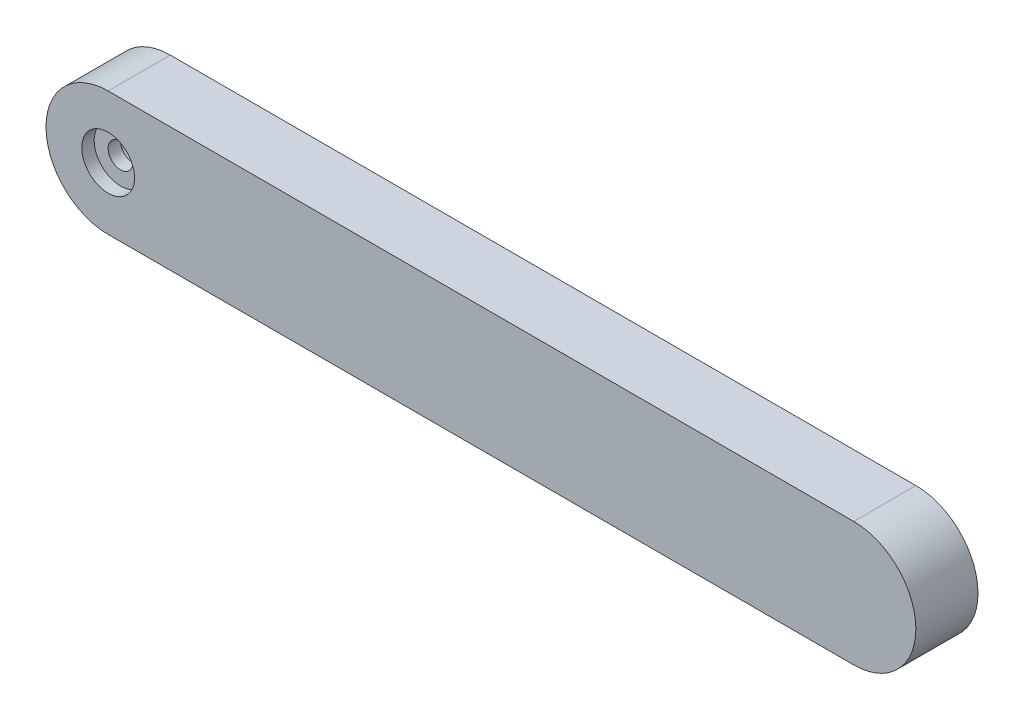
SolidWorks part; units mm, degrees
ref_plane "Front" through (0, 0, 0) normal (0, 0, 1) x (1, 0, 0)
ref_plane "Top" through (0, 0, 0) normal (0, 1, 0) x (1, 0, 0)
ref_plane "Right" through (0, 0, 0) normal (1, 0, 0) x (0, 0, -1)
sketch "Sketch1" plane through (0, 0, 0) normal (0, 0, 1) x (1, 0, 0)
  line L0 (0, 0) -> (60, 0) construction
  line L1 (0, 5) -> (60, 5)
  line L2 (0, -5) -> (60, -5)
  arc A0 (0, 5) -> (0, -5) centre (0, 0) ccw
  arc A1 (60, -5) -> (60, 5) centre (60, 0) ccw
  point P3 (30, 0)
  dimension "D2" = 5
  dimension "D1" = 60
extrude "Boss-Extrude1" add sketch "Sketch1" along normal blind 5 contours L1 A1 L2 A0
sketch "Sketch2" plane through (0, 0, 0) normal (0, 0, -1) x (-1, 0, 0)
  circle A0 centre (0, 0) radius 2.0125
  dimension "D1" = 4.025
extrude "Cut-Extrude1" cut sketch "Sketch2" against normal blind 3
sketch "Sketch3" plane through (0, 0, 5) normal (0, 0, 1) x (1, 0, 0)
  circle A0 centre (0, 0) radius 2.125
  dimension "D1" = 4.25
extrude "Cut-Extrude2" cut sketch "Sketch3" against normal blind 1 contours A0
sketch "Sketch4" plane through (0, 0, 4) normal (0, 0, 1) x (1, 0, 0)
  circle A0 centre (0, 0) radius 1
  dimension "D1" = 2
extrude "Cut-Extrude3" cut sketch "Sketch4" against normal through all contours A0
ref_axis "Axis1" through (60, 0, 5) along (0, 0, -1)
equation "\"LENGTH\"= 60mm"
equation "\"D1@Sketch1\"=\"LENGTH\""
